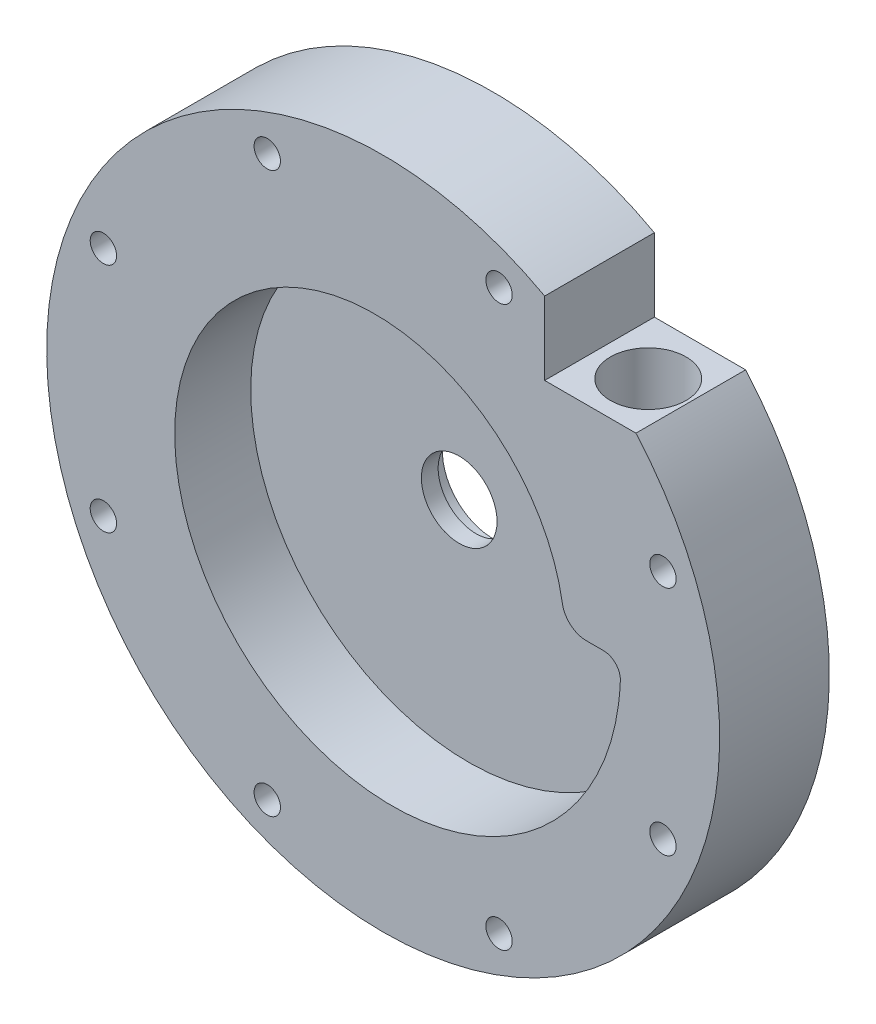
SolidWorks part; units mm, degrees
material "6061-T6 (SS)"
ref_plane "Front Plane" through (0, 0, 0) normal (0, 0, 1) x (1, 0, 0)
ref_plane "Top Plane" through (0, 0, 0) normal (0, 1, 0) x (1, 0, 0)
ref_plane "Right Plane" through (0, 0, 0) normal (1, 0, 0) x (0, 0, -1)
sketch "Sketch22" plane through (0, 0, 0) normal (0, 1, 0) x (1, 0, 0)
  line L0 (-25.4, 0) -> (-7.1437, 0)
  line L1 (-25.4, 0) -> (-25.4, -14.351)
  line L2 (-9.525, 6.35) -> (-9.525, 3.175)
  line L3 (-25.4, -14.351) -> (-63.5, -14.351)
  line L4 (-63.5, -14.351) -> (-63.5, 6.35)
  line L6 (-9.525, 3.175) -> (-7.1437, 3.175)
  line L9 (-9.525, 6.35) -> (-63.5, 6.35)
  line L10 (0, 0) -> (0, 9.525) construction
  line L11 (-7.1437, 3.175) -> (-7.1437, 0)
  dimension "D1" = 6.35
  dimension "D2" = 3.175
  dimension "D3" = 14.351
  dimension "D4" = 19.05
  dimension "D5" = 50.8
  dimension "D6" = 127
  dimension "D7" = 14.2875
revolve "Main Body" add sketch "Sketch22" angle 360 about L10
curve "Volute Spiral"
sketch "Sketch23" plane through (0, 0, 0) normal (0, 0, 1) x (1, 0, 0)
  line L1 (38.3384, 3.3047) -> (41.5935, 3.3047)
  arc A5 (34.2618, 0) -> (35.1661, 0) centre (34.714, -0.0185) ccw
  arc A6 (35.1661, 0) -> (38.3384, 3.3047) centre (38.3384, 0.1297) cw
  arc A7 (41.5935, 3.3047) -> (44.7632, 0) centre (41.5935, 0.1322) cw
  spline S1 degree 3 poles (2030.2811, -117.0653) (22.7633, -27.2168) (33.8126, -13.6289) (34.2778, 0.4312) (34.2837, 0.647) (34.2927, 1.0788) (34.2982, 2.0882) (34.2447, 3.6037) (34.0848, 5.4046) (33.8442, 7.1278) (33.5167, 8.8404) (33.1027, 10.5382) (32.6028, 12.2167) (32.018, 13.8717) (31.3492, 15.4988) (30.5978, 17.0937) (29.7654, 18.6523) (28.8536, 20.1705) (27.8645, 21.6442) (26.8001, 23.0695) (25.6629, 24.4425) (24.4554, 25.7594) (23.1804, 27.0168) (21.8408, 28.2111) (20.4397, 29.3391) (18.9803, 30.3974) (17.4663, 31.3832) (15.901, 32.2936) (14.2884, 33.126) (12.6323, 33.8779) (10.9367, 34.5469) (9.2057, 35.1311) (7.4437, 35.6286) (5.6549, 36.0377) (3.8437, 36.3569) (2.0147, 36.5852) (0.1725, 36.7214) (-1.6783, 36.7648) (-3.533, 36.7149) (-5.387, 36.5715) (-7.2355, 36.3344) (-9.0737, 36.0038) (-10.8971, 35.5803) (-12.7007, 35.0643) (-14.48, 34.457) (-16.2304, 33.7593) (-17.9471, 32.9726) (-19.6258, 32.0987) (-21.262, 31.1393) (-22.8513, 30.0964) (-24.3894, 28.9724) (-25.8723, 27.7699) (-27.2958, 26.4914) (-28.6562, 25.1399) (-29.9497, 23.7185) (-31.1726, 22.2307) (-32.3216, 20.6797) (-33.3934, 19.0694) (-34.385, 17.4036) (-35.2934, 15.6863) (-36.116, 13.9216) (-36.8503, 12.1138) (-37.4941, 10.2673) (-38.0454, 8.3867) (-38.5022, 6.4766) (-38.8631, 4.5417) (-39.1267, 2.587) (-39.292, 0.6172) (-39.358, -1.3627) (-39.3242, -3.3477) (-39.1902, -5.3327) (-38.956, -7.3127) (-38.6217, -9.2826) (-38.1877, -11.2374) (-37.6547, -13.172) (-37.0237, -15.0814) (-36.2958, -16.9606) (-35.4725, -18.8047) (-34.5554, -20.6088) (-33.5465, -22.3683) (-32.448, -24.0784) (-31.2623, -25.7345) (-29.9921, -27.3322) (-28.6401, -28.8672) (-27.2096, -30.3353) (-25.7038, -31.7324) (-24.1262, -33.0548) (-22.4806, -34.2987) (-20.7709, -35.4607) (-19.0011, -36.5374) (-17.1755, -37.5256) (-15.2985, -38.4226) (-13.3748, -39.2257) (-11.4089, -39.9324) (-9.4058, -40.5405) (-7.3703, -41.048) (-5.3076, -41.4533) (-3.2227, -41.7548) (-1.1209, -41.9515) (0.9925, -42.0422) (3.1122, -42.0264) (5.2328, -41.9037) (7.349, -41.6739) (9.4552, -41.3371) (11.5462, -40.8938) (13.6164, -40.3447) (15.6606, -39.6907) (17.6735, -38.9331) (19.6497, -38.0733) (21.5841, -37.1132) (23.4715, -36.0547) (25.3071, -34.9002) (27.0859, -33.6522) (28.8031, -32.3134) (30.4541, -30.887) (32.0344, -29.3763) (33.5397, -27.7846) (34.9659, -26.1158) (36.309, -24.3737) (37.5652, -22.5626) (38.7311, -20.6867) (39.8032, -18.7505) (40.7784, -16.7589) (41.6539, -14.7165) (42.4271, -12.6284) (43.0955, -10.4997) (43.657, -8.3358) (44.1098, -6.1419) (44.4379, -4.0162) (44.6062, -2.4335) (44.6789, -1.4992) (44.7044, -1.1249) (44.7219, -0.8439) (44.7375, -0.5628) (45.566, 16.1056) (34.6961, 33.2048) (2043.9061, -40.4097) knots -0.16783 -0.16783 -0.16783 -0.16783 0.000871 0.001743 0.002614 0.003486 0.006976 0.014843 0.021852 0.028876 0.035916 0.042971 0.050042 0.057129 0.064232 0.07135 0.078484 0.085634 0.0928 0.099981 0.107179 0.114393 0.121623 0.128869 0.136131 0.143409 0.150703 0.158014 0.165341 0.172684 0.180044 0.187419 0.194812 0.20222 0.209645 0.217087 0.224545 0.232019 0.23951 0.247018 0.254542 0.262083 0.26964 0.277214 0.284805 0.292413 0.300037 0.307678 0.315336 0.32301 0.330702 0.33841 0.346135 0.353877 0.361636 0.369412 0.377205 0.385015 0.392841 0.400685 0.408546 0.416424 0.424319 0.432231 0.440161 0.448107 0.456071 0.464051 0.472049 0.480065 0.488097 0.496147 0.504214 0.512298 0.5204 0.528519 0.536655 0.544809 0.55298 0.561169 0.569375 0.577598 0.585839 0.594097 0.602373 0.610667 0.618977 0.627306 0.635652 0.644016 0.652397 0.660796 0.669212 0.677647 0.686099 0.694568 0.703055 0.71156 0.720083 0.728624 0.737182 0.745758 0.754352 0.762964 0.771593 0.780241 0.788906 0.797589 0.80629 0.815009 0.823746 0.832501 0.841274 0.850065 0.858874 0.867701 0.876546 0.885409 0.89429 0.903189 0.912106 0.921041 0.929995 0.938966 0.947956 0.956964 0.96599 0.975034 0.984097 0.992041 0.994314 0.995451 0.996587 0.997725 0.998862 1.198789 1.198789 1.198789 1.198789 only from (34.2618, 0) to (44.7632, 0) construction
  spline S2 degree 3 poles (34.2618, 0) (34.2648, 0.0718) (34.2707, 0.2156) (34.2778, 0.4312) (34.2837, 0.647) (34.2927, 1.0788) (34.2982, 2.0882) (34.2447, 3.6037) (34.0848, 5.4046) (33.8442, 7.1278) (33.5167, 8.8404) (33.1027, 10.5382) (32.6028, 12.2167) (32.018, 13.8717) (31.3492, 15.4988) (30.5978, 17.0937) (29.7654, 18.6523) (28.8536, 20.1705) (27.8645, 21.6442) (26.8001, 23.0695) (25.6629, 24.4425) (24.4554, 25.7594) (23.1804, 27.0168) (21.8408, 28.2111) (20.4397, 29.3391) (18.9803, 30.3974) (17.4663, 31.3832) (15.901, 32.2936) (14.2884, 33.126) (12.6323, 33.8779) (10.9367, 34.5469) (9.2057, 35.1311) (7.4437, 35.6286) (5.6549, 36.0377) (3.8437, 36.3569) (2.0147, 36.5852) (0.1725, 36.7214) (-1.6783, 36.7648) (-3.533, 36.7149) (-5.387, 36.5715) (-7.2355, 36.3344) (-9.0737, 36.0038) (-10.8971, 35.5803) (-12.7007, 35.0643) (-14.48, 34.457) (-16.2304, 33.7593) (-17.9471, 32.9726) (-19.6258, 32.0987) (-21.262, 31.1393) (-22.8513, 30.0964) (-24.3894, 28.9724) (-25.8723, 27.7699) (-27.2958, 26.4914) (-28.6562, 25.1399) (-29.9497, 23.7185) (-31.1726, 22.2307) (-32.3216, 20.6797) (-33.3934, 19.0694) (-34.385, 17.4036) (-35.2934, 15.6863) (-36.116, 13.9216) (-36.8503, 12.1138) (-37.4941, 10.2673) (-38.0454, 8.3867) (-38.5022, 6.4766) (-38.8631, 4.5417) (-39.1267, 2.587) (-39.292, 0.6172) (-39.358, -1.3627) (-39.3242, -3.3477) (-39.1902, -5.3327) (-38.956, -7.3127) (-38.6217, -9.2826) (-38.1877, -11.2374) (-37.6547, -13.172) (-37.0237, -15.0814) (-36.2958, -16.9606) (-35.4725, -18.8047) (-34.5554, -20.6088) (-33.5465, -22.3683) (-32.448, -24.0784) (-31.2623, -25.7345) (-29.9921, -27.3322) (-28.6401, -28.8672) (-27.2096, -30.3353) (-25.7038, -31.7324) (-24.1262, -33.0548) (-22.4806, -34.2987) (-20.7709, -35.4607) (-19.0011, -36.5374) (-17.1755, -37.5256) (-15.2985, -38.4226) (-13.3748, -39.2257) (-11.4089, -39.9324) (-9.4058, -40.5405) (-7.3703, -41.048) (-5.3076, -41.4533) (-3.2227, -41.7548) (-1.1209, -41.9515) (0.9925, -42.0422) (3.1122, -42.0264) (5.2328, -41.9037) (7.349, -41.6739) (9.4552, -41.3371) (11.5462, -40.8938) (13.6164, -40.3447) (15.6606, -39.6907) (17.6735, -38.9331) (19.6497, -38.0733) (21.5841, -37.1132) (23.4715, -36.0547) (25.3071, -34.9002) (27.0859, -33.6522) (28.8031, -32.3134) (30.4541, -30.887) (32.0344, -29.3763) (33.5397, -27.7846) (34.9659, -26.1158) (36.309, -24.3737) (37.5652, -22.5626) (38.7311, -20.6867) (39.8032, -18.7505) (40.7784, -16.7589) (41.6539, -14.7165) (42.4271, -12.6284) (43.0955, -10.4997) (43.657, -8.3358) (44.1098, -6.1419) (44.4379, -4.0162) (44.6062, -2.4335) (44.6789, -1.4992) (44.7044, -1.1249) (44.7219, -0.8439) (44.7375, -0.5628) (44.7515, -0.2815) (44.7593, -0.0938) (44.7632, 0) knots 0 0 0 0 0.000871 0.001743 0.002614 0.003486 0.006976 0.014843 0.021852 0.028876 0.035916 0.042971 0.050042 0.057129 0.064232 0.07135 0.078484 0.085634 0.0928 0.099981 0.107179 0.114393 0.121623 0.128869 0.136131 0.143409 0.150703 0.158014 0.165341 0.172684 0.180044 0.187419 0.194812 0.20222 0.209645 0.217087 0.224545 0.232019 0.23951 0.247018 0.254542 0.262083 0.26964 0.277214 0.284805 0.292413 0.300037 0.307678 0.315336 0.32301 0.330702 0.33841 0.346135 0.353877 0.361636 0.369412 0.377205 0.385015 0.392841 0.400685 0.408546 0.416424 0.424319 0.432231 0.440161 0.448107 0.456071 0.464051 0.472049 0.480065 0.488097 0.496147 0.504214 0.512298 0.5204 0.528519 0.536655 0.544809 0.55298 0.561169 0.569375 0.577598 0.585839 0.594097 0.602373 0.610667 0.618977 0.627306 0.635652 0.644016 0.652397 0.660796 0.669212 0.677647 0.686099 0.694568 0.703055 0.71156 0.720083 0.728624 0.737182 0.745758 0.754352 0.762964 0.771593 0.780241 0.788906 0.797589 0.80629 0.815009 0.823746 0.832501 0.841274 0.850065 0.858874 0.867701 0.876546 0.885409 0.89429 0.903189 0.912106 0.921041 0.929995 0.938966 0.947956 0.956964 0.96599 0.975034 0.984097 0.992041 0.994314 0.995451 0.996587 0.997725 0.998862 1 1 1 1
  dimension "D1" = 0.9042
  dimension "D2" = 3.175
extrude "Volute Cut" cut sketch "Sketch23" along normal through all
ref_plane "Volute Height Plane" through (0, 0, 8.5801) normal (0, 0, 1) x (1, 0, 0)
sketch "Sketch25" plane through (0, 0, 8.5801) normal (0, 0, 1) x (1, 0, 0)
  line L0 (38.3384, 3.3047) -> (41.5935, 3.3047)
  arc A0 (34.2618, 0) -> (35.1661, 0) centre (34.714, -0.0185) ccw
  arc A7 (35.1661, 0) -> (38.3384, 3.3047) centre (38.3384, 0.1297) cw
  arc A8 (41.5935, 3.3047) -> (44.7632, 0) centre (41.5935, 0.1322) cw
  arc A10 (38.3384, 3.3047) -> (33.8292, 7.1291) centre (38.3384, 7.8752) cw
  spline S2 degree 3 poles (2030.2811, -117.0653) (22.7633, -27.2168) (33.8126, -13.6289) (34.2778, 0.4312) (34.2837, 0.647) (34.2927, 1.0788) (34.2982, 2.0882) (34.2447, 3.6037) (34.0848, 5.4046) (33.8442, 7.1278) (33.5167, 8.8404) (33.1027, 10.5382) (32.6028, 12.2167) (32.018, 13.8717) (31.3492, 15.4988) (30.5978, 17.0937) (29.7654, 18.6523) (28.8536, 20.1705) (27.8645, 21.6442) (26.8001, 23.0695) (25.6629, 24.4425) (24.4554, 25.7594) (23.1804, 27.0168) (21.8408, 28.2111) (20.4397, 29.3391) (18.9803, 30.3974) (17.4663, 31.3832) (15.901, 32.2936) (14.2884, 33.126) (12.6323, 33.8779) (10.9367, 34.5469) (9.2057, 35.1311) (7.4437, 35.6286) (5.6549, 36.0377) (3.8437, 36.3569) (2.0147, 36.5852) (0.1725, 36.7214) (-1.6783, 36.7648) (-3.533, 36.7149) (-5.387, 36.5715) (-7.2355, 36.3344) (-9.0737, 36.0038) (-10.8971, 35.5803) (-12.7007, 35.0643) (-14.48, 34.457) (-16.2304, 33.7593) (-17.9471, 32.9726) (-19.6258, 32.0987) (-21.262, 31.1393) (-22.8513, 30.0964) (-24.3894, 28.9724) (-25.8723, 27.7699) (-27.2958, 26.4914) (-28.6562, 25.1399) (-29.9497, 23.7185) (-31.1726, 22.2307) (-32.3216, 20.6797) (-33.3934, 19.0694) (-34.385, 17.4036) (-35.2934, 15.6863) (-36.116, 13.9216) (-36.8503, 12.1138) (-37.4941, 10.2673) (-38.0454, 8.3867) (-38.5022, 6.4766) (-38.8631, 4.5417) (-39.1267, 2.587) (-39.292, 0.6172) (-39.358, -1.3627) (-39.3242, -3.3477) (-39.1902, -5.3327) (-38.956, -7.3127) (-38.6217, -9.2826) (-38.1877, -11.2374) (-37.6547, -13.172) (-37.0237, -15.0814) (-36.2958, -16.9606) (-35.4725, -18.8047) (-34.5554, -20.6088) (-33.5465, -22.3683) (-32.448, -24.0784) (-31.2623, -25.7345) (-29.9921, -27.3322) (-28.6401, -28.8672) (-27.2096, -30.3353) (-25.7038, -31.7324) (-24.1262, -33.0548) (-22.4806, -34.2987) (-20.7709, -35.4607) (-19.0011, -36.5374) (-17.1755, -37.5256) (-15.2985, -38.4226) (-13.3748, -39.2257) (-11.4089, -39.9324) (-9.4058, -40.5405) (-7.3703, -41.048) (-5.3076, -41.4533) (-3.2227, -41.7548) (-1.1209, -41.9515) (0.9925, -42.0422) (3.1122, -42.0264) (5.2328, -41.9037) (7.349, -41.6739) (9.4552, -41.3371) (11.5462, -40.8938) (13.6164, -40.3447) (15.6606, -39.6907) (17.6735, -38.9331) (19.6497, -38.0733) (21.5841, -37.1132) (23.4715, -36.0547) (25.3071, -34.9002) (27.0859, -33.6522) (28.8031, -32.3134) (30.4541, -30.887) (32.0344, -29.3763) (33.5397, -27.7846) (34.9659, -26.1158) (36.309, -24.3737) (37.5652, -22.5626) (38.7311, -20.6867) (39.8032, -18.7505) (40.7784, -16.7589) (41.6539, -14.7165) (42.4271, -12.6284) (43.0955, -10.4997) (43.657, -8.3358) (44.1098, -6.1419) (44.4379, -4.0162) (44.6062, -2.4335) (44.6789, -1.4992) (44.7044, -1.1249) (44.7219, -0.8439) (44.7375, -0.5628) (45.566, 16.1056) (34.6961, 33.2048) (2043.9061, -40.4097) knots -0.16783 -0.16783 -0.16783 -0.16783 0.000871 0.001743 0.002614 0.003486 0.006976 0.014843 0.021852 0.028876 0.035916 0.042971 0.050042 0.057129 0.064232 0.07135 0.078484 0.085634 0.0928 0.099981 0.107179 0.114393 0.121623 0.128869 0.136131 0.143409 0.150703 0.158014 0.165341 0.172684 0.180044 0.187419 0.194812 0.20222 0.209645 0.217087 0.224545 0.232019 0.23951 0.247018 0.254542 0.262083 0.26964 0.277214 0.284805 0.292413 0.300037 0.307678 0.315336 0.32301 0.330702 0.33841 0.346135 0.353877 0.361636 0.369412 0.377205 0.385015 0.392841 0.400685 0.408546 0.416424 0.424319 0.432231 0.440161 0.448107 0.456071 0.464051 0.472049 0.480065 0.488097 0.496147 0.504214 0.512298 0.5204 0.528519 0.536655 0.544809 0.55298 0.561169 0.569375 0.577598 0.585839 0.594097 0.602373 0.610667 0.618977 0.627306 0.635652 0.644016 0.652397 0.660796 0.669212 0.677647 0.686099 0.694568 0.703055 0.71156 0.720083 0.728624 0.737182 0.745758 0.754352 0.762964 0.771593 0.780241 0.788906 0.797589 0.80629 0.815009 0.823746 0.832501 0.841274 0.850065 0.858874 0.867701 0.876546 0.885409 0.89429 0.903189 0.912106 0.921041 0.929995 0.938966 0.947956 0.956964 0.96599 0.975034 0.984097 0.992041 0.994314 0.995451 0.996587 0.997725 0.998862 1.198789 1.198789 1.198789 1.198789 only from (34.2618, 0) to (44.7632, 0) construction
  spline S3 degree 3 poles (34.2618, 0) (34.2648, 0.0718) (34.2707, 0.2156) (34.2778, 0.4312) (34.2837, 0.647) (34.2927, 1.0788) (34.2982, 2.0882) (34.2447, 3.6037) (34.0848, 5.4046) (33.8442, 7.1278) (33.5167, 8.8404) (33.1027, 10.5382) (32.6028, 12.2167) (32.018, 13.8717) (31.3492, 15.4988) (30.5978, 17.0937) (29.7654, 18.6523) (28.8536, 20.1705) (27.8645, 21.6442) (26.8001, 23.0695) (25.6629, 24.4425) (24.4554, 25.7594) (23.1804, 27.0168) (21.8408, 28.2111) (20.4397, 29.3391) (18.9803, 30.3974) (17.4663, 31.3832) (15.901, 32.2936) (14.2884, 33.126) (12.6323, 33.8779) (10.9367, 34.5469) (9.2057, 35.1311) (7.4437, 35.6286) (5.6549, 36.0377) (3.8437, 36.3569) (2.0147, 36.5852) (0.1725, 36.7214) (-1.6783, 36.7648) (-3.533, 36.7149) (-5.387, 36.5715) (-7.2355, 36.3344) (-9.0737, 36.0038) (-10.8971, 35.5803) (-12.7007, 35.0643) (-14.48, 34.457) (-16.2304, 33.7593) (-17.9471, 32.9726) (-19.6258, 32.0987) (-21.262, 31.1393) (-22.8513, 30.0964) (-24.3894, 28.9724) (-25.8723, 27.7699) (-27.2958, 26.4914) (-28.6562, 25.1399) (-29.9497, 23.7185) (-31.1726, 22.2307) (-32.3216, 20.6797) (-33.3934, 19.0694) (-34.385, 17.4036) (-35.2934, 15.6863) (-36.116, 13.9216) (-36.8503, 12.1138) (-37.4941, 10.2673) (-38.0454, 8.3867) (-38.5022, 6.4766) (-38.8631, 4.5417) (-39.1267, 2.587) (-39.292, 0.6172) (-39.358, -1.3627) (-39.3242, -3.3477) (-39.1902, -5.3327) (-38.956, -7.3127) (-38.6217, -9.2826) (-38.1877, -11.2374) (-37.6547, -13.172) (-37.0237, -15.0814) (-36.2958, -16.9606) (-35.4725, -18.8047) (-34.5554, -20.6088) (-33.5465, -22.3683) (-32.448, -24.0784) (-31.2623, -25.7345) (-29.9921, -27.3322) (-28.6401, -28.8672) (-27.2096, -30.3353) (-25.7038, -31.7324) (-24.1262, -33.0548) (-22.4806, -34.2987) (-20.7709, -35.4607) (-19.0011, -36.5374) (-17.1755, -37.5256) (-15.2985, -38.4226) (-13.3748, -39.2257) (-11.4089, -39.9324) (-9.4058, -40.5405) (-7.3703, -41.048) (-5.3076, -41.4533) (-3.2227, -41.7548) (-1.1209, -41.9515) (0.9925, -42.0422) (3.1122, -42.0264) (5.2328, -41.9037) (7.349, -41.6739) (9.4552, -41.3371) (11.5462, -40.8938) (13.6164, -40.3447) (15.6606, -39.6907) (17.6735, -38.9331) (19.6497, -38.0733) (21.5841, -37.1132) (23.4715, -36.0547) (25.3071, -34.9002) (27.0859, -33.6522) (28.8031, -32.3134) (30.4541, -30.887) (32.0344, -29.3763) (33.5397, -27.7846) (34.9659, -26.1158) (36.309, -24.3737) (37.5652, -22.5626) (38.7311, -20.6867) (39.8032, -18.7505) (40.7784, -16.7589) (41.6539, -14.7165) (42.4271, -12.6284) (43.0955, -10.4997) (43.657, -8.3358) (44.1098, -6.1419) (44.4379, -4.0162) (44.6062, -2.4335) (44.6789, -1.4992) (44.7044, -1.1249) (44.7219, -0.8439) (44.7375, -0.5628) (44.7515, -0.2815) (44.7593, -0.0938) (44.7632, 0) knots 0 0 0 0 0.000871 0.001743 0.002614 0.003486 0.006976 0.014843 0.021852 0.028876 0.035916 0.042971 0.050042 0.057129 0.064232 0.07135 0.078484 0.085634 0.0928 0.099981 0.107179 0.114393 0.121623 0.128869 0.136131 0.143409 0.150703 0.158014 0.165341 0.172684 0.180044 0.187419 0.194812 0.20222 0.209645 0.217087 0.224545 0.232019 0.23951 0.247018 0.254542 0.262083 0.26964 0.277214 0.284805 0.292413 0.300037 0.307678 0.315336 0.32301 0.330702 0.33841 0.346135 0.353877 0.361636 0.369412 0.377205 0.385015 0.392841 0.400685 0.408546 0.416424 0.424319 0.432231 0.440161 0.448107 0.456071 0.464051 0.472049 0.480065 0.488097 0.496147 0.504214 0.512298 0.5204 0.528519 0.536655 0.544809 0.55298 0.561169 0.569375 0.577598 0.585839 0.594097 0.602373 0.610667 0.618977 0.627306 0.635652 0.644016 0.652397 0.660796 0.669212 0.677647 0.686099 0.694568 0.703055 0.71156 0.720083 0.728624 0.737182 0.745758 0.754352 0.762964 0.771593 0.780241 0.788906 0.797589 0.80629 0.815009 0.823746 0.832501 0.841274 0.850065 0.858874 0.867701 0.876546 0.885409 0.89429 0.903189 0.912106 0.921041 0.929995 0.938966 0.947956 0.956964 0.96599 0.975034 0.984097 0.992041 0.994314 0.995451 0.996587 0.997725 0.998862 1 1 1 1
  dimension "D1" = 3.175
  dimension "D2" = 0.9042
extrude "Cap Cut" cut sketch "Sketch25" along normal through all contours S3 A0 A7 A10 | A0 S3 A8 L0 A7 region at (0.5826, -3.3219, 8.5801) region at (35.147, 2.7612, 8.5801)
sketch "Sketch28" plane through (0, 0, 14.351) normal (0, 0, 1) x (1, 0, 0)
  line L1 (30.48, 55.7065) -> (47.7054, 55.7065)
  line L2 (30.48, 55.7065) -> (30.48, 41.91)
  line L3 (30.48, 41.91) -> (47.7054, 41.91)
  line L4 (47.7054, 55.7065) -> (47.7054, 41.91)
  circle A1 centre (0, 0) radius 63.5 construction
  dimension "D1" = 41.91
  dimension "D2" = 30.48
extrude "Outlet Hole Cut" cut sketch "Sketch28" against normal through all
hole_wizard "Outlet Hole" positions "3DSketch2" profile "Sketch20" hole size "3/8" standard "ANSI Inch"
sketch3d "3DSketch2"
  line L0 (41.5935, 3.3047, 0) -> (38.3384, 3.3047, 8.5801) construction
  point P0 (39.966, 3.3047, 4.2901)
  point P11 (39.966, 3.3047, 4.2901)
  point P20 (39.966, 3.3047, 4.2901)
  point P22 (39.966, 41.91, 4.2901)
sketch "Sketch20" plane through (39.966, 41.91, 4.2901) normal (1, 0, 0) x (0, 0, 1)
  line L0 (0, 0) -> (0, 44.7716)
  line L1 (0, 44.7716) -> (4.7625, 41.91)
  line L2 (4.7625, 41.91) -> (4.7625, 0)
  line L5 (4.7625, 0) -> (0, 0)
  line L10 (0, 44.7716) -> (-4.7625, 41.91) construction
  line L11 (0, -6.35) -> (0, 107.95) construction
  dimension "Hole Dia." = 9.525
  dimension "Hole Depth" = 41.91
  dimension "Drill Angle" = 118
hole_wizard "Pipe Tap Drill for 3/8 Tap1" positions "3DSketch4" profile "Sketch29" hole size "3/8" standard "ANSI Inch"
sketch3d "3DSketch4"
  circle A0 centre (39.966, 41.91, 4.2901) radius 4.7625 construction
  point P0 (39.966, 41.91, 4.2901)
  point P6 (39.966, 46.6725, 4.2901)
sketch "Sketch29" plane through (39.966, 41.91, 4.2901) normal (1, 0, 0) x (0, 0, 1)
  line L0 (0, 0) -> (0, 16.9886)
  line L1 (0, 16.9886) -> (7.1374, 12.7)
  line L2 (7.1374, 12.7) -> (7.1374, 0)
  line L5 (7.1374, 0) -> (0, 0)
  line L10 (0, 16.9886) -> (-7.1374, 12.7) construction
  line L11 (0, -6.35) -> (0, 107.95) construction
  dimension "Hole Dia." = 14.2748
  dimension "Hole Depth" = 12.7
  dimension "Drill Angle" = 118
sketch "Sketch26" plane through (0, 0, 14.351) normal (0, 0, 1) x (1, 0, 0)
  line L0 (52.7997, -21.8704) -> (58.6664, -24.3004) construction
  line L1 (63.5, 0) -> (0, 0) construction
  circle A0 centre (52.7997, -21.8704) radius 2.4892
  circle A1 centre (0, 0) radius 63.5 construction
  dimension "D1" = 4.9784
  dimension "D2" = 6.35
  dimension "D3" = 22.5
extrude "Fastener Hole" cut sketch "Sketch26" against normal through all
pattern_circular "Fastener Holes" count 8 over 360 about axis through (0, 0, 0) along (0, 0, 1) of "Fastener Hole"
ref_axis "Axis1" through (0, 0, -6.35) along (0, 0, 1)
ref_plane "Plane1" through (0, 0, 0) normal (0, 1, 0) x (0, 0, 1)
